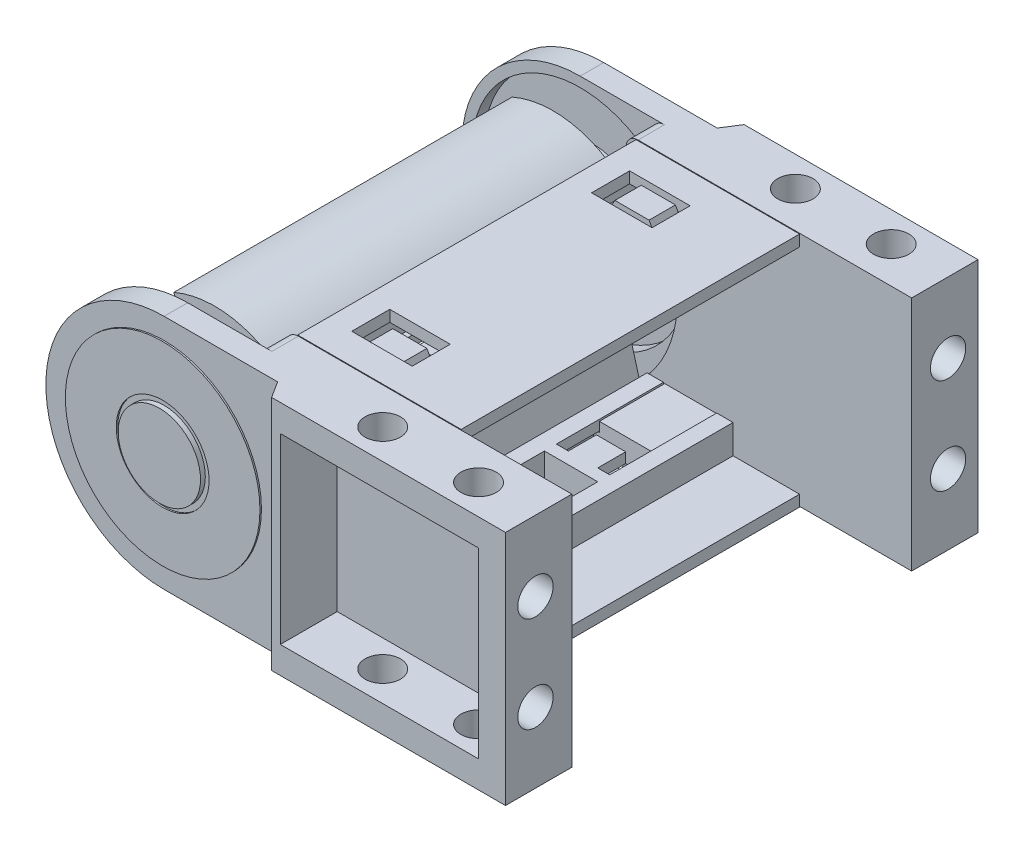
SolidWorks part; units mm, degrees
material "ABS"
ref_plane "Front Plane" through (0, 0, 0) normal (0, 0, 1) x (1, 0, 0)
ref_plane "Top Plane" through (0, 0, 0) normal (0, 1, 0) x (1, 0, 0)
ref_plane "Right Plane" through (0, 0, 0) normal (1, 0, 0) x (0, 0, -1)
sketch "Sketch1" plane through (0, 0, 0) normal (0, 0, 1) x (1, 0, 0)
  line L0 (0, 19.75) -> (59.75, 19.75)
  line L1 (59.75, 19.75) -> (59.75, -19.75)
  line L2 (59.75, -19.75) -> (0, -19.75)
  arc A0 (0, 19.75) -> (0, -19.75) centre (0, 0) ccw
  point P1 (-19.75, 0)
  dimension "D1" = 39.5
  dimension "D2" = 79.5
extrude "Boss-Extrude1" add sketch "Sketch1" against normal blind 11.08 from offset 39.45
sketch "Sketch2" plane through (0, 0, 39.45) normal (0, 0, 1) x (1, 0, 0)
  line L0 (59.75, -19.75) -> (59.75, 19.75) construction
  line L1 (22.15, 15.25) -> (55.25, 15.25)
  line L2 (22.15, 15.25) -> (22.15, -15.25)
  line L3 (22.15, -15.25) -> (55.25, -15.25)
  line L4 (55.25, 15.25) -> (55.25, -15.25)
  line L5 (38.7, -15.25) -> (38.7, 15.25) construction
  line L6 (22.15, 0) -> (55.25, 0) construction
  line L7 (59.75, 19.75) -> (0, 19.75) construction
  point P0 (38.7, 0)
  dimension "D1" = 4.5
  dimension "D2" = 4.5
  dimension "D3" = 33.1
extrude "Cut-Extrude1" cut sketch "Sketch2" against normal blind 9.5
sketch "Sketch3" plane through (0, 0, 39.45) normal (0, 0, 1) x (1, 0, 0)
  line L0 (0, -19.75) -> (59.75, -19.75) construction
  line L1 (59.75, 19.75) -> (0, 19.75) construction
  line L2 (0, -19.75) -> (18.95, -19.75)
  line L3 (18.95, 19.75) -> (0, 19.75)
  line L4 (18.95, 19.75) -> (18.95, -19.75)
  line L5 (59.75, -19.75) -> (59.75, 19.75) construction
  arc A0 (0, 19.75) -> (0, -19.75) centre (0, 0) ccw construction
  arc A1 (0, 19.75) -> (0, -19.75) centre (0, 0) ccw
  point P7 (-19.75, 0)
  dimension "D1" = 40.8
extrude "Cut-Extrude2" cut sketch "Sketch3" against normal blind 2.75
chamfer "Chamfer1" distance 1.75 distance2 2.75 1 edges at (18.95, 0, 39.45) first distance on face at (39.35, 0, 39.45)
sketch "Sketch5" plane through (0, 0, 36.7) normal (0, 0, 1) x (1, 0, 0)
  circle A0 centre (0, 0) radius 7.75
  circle A1 centre (0, 0) radius 16.25
  circle A2 centre (0, 0) radius 5.15
  dimension "D1" = 10.3
  dimension "D2" = 15.5
  dimension "D3" = 32.5
extrude "Boss-Extrude2" add sketch "Sketch5" along normal blind 0.25 contours A1 A0 region at (-15.7904, 0, 36.7)
extrude "Cut-Extrude3" cut sketch "Sketch5<3>" against normal through all contours A2 region at (0, 0, 36.7)
sketch "Sketch5<3>" plane through (0, 0, 36.7) normal (0, 0, 1) x (1, 0, 0) same geometry as "Sketch5"
sketch "Sketch6" plane through (0, 19.75, 0) normal (0, 1, 0) x (1, 0, 0)
  line L0 (59.75, -34.45) -> (20.7, -34.45) construction
  line L1 (59.75, -28.37) -> (59.75, -39.45) construction
  line L3 (59.75, -39.45) -> (20.7, -39.45) construction
  circle A0 centre (50.25, -34.45) radius 2.95
  circle A1 centre (34.25, -34.45) radius 2.95
  point P9 (0, 0)
  point P12 (0, 0)
  dimension "D1" = 5.9
  dimension "D2" = 16
  dimension "D3" = 9.5
  dimension "D4" = 5
extrude "Cut-Extrude4" cut sketch "Sketch6" against normal through all
sketch "Sketch7" plane through (59.75, 0, 0) normal (1, 0, 0) x (0, 0, -1)
  line L0 (-34.45, 19.75) -> (-34.45, -19.75) construction
  line L1 (-28.37, 19.75) -> (-39.45, 19.75) construction
  line L2 (-28.37, -19.75) -> (-39.45, -19.75) construction
  line L3 (-34.45, 0) -> (-28.37, 0) construction
  line L4 (-28.37, -19.75) -> (-28.37, 19.75) construction
  line L5 (-39.45, -19.75) -> (-39.45, 19.75) construction
  circle A0 centre (-34.45, 8) radius 2.95
  circle A1 centre (-34.45, -8) radius 2.95
  dimension "D1" = 16
  dimension "D2" = 5.9
  dimension "D3" = 5
extrude "Cut-Extrude5" cut sketch "Sketch7" against normal up to next
sketch "Sketch8" plane through (0, 0, 28.37) normal (0, 0, -1) x (-1, 0, 0)
  line L0 (19.75, 0) -> (-20.65, 0) construction
  circle A0 centre (0, 0) radius 20.65
  arc A1 (0, -19.75) -> (0, 19.75) centre (0, 0) ccw construction
  point P3 (-20.65, 0)
  point P4 (19.75, 0)
  dimension "D1" = 40.4
extrude "Cut-Extrude6" cut sketch "Sketch8" against normal blind 4.4
sketch "Sketch9" plane through (0, 0, 32.77) normal (0, 0, -1) x (-1, 0, 0)
  circle A0 centre (0, 0) radius 18.1
  dimension "D1" = 36.2
extrude "Cut-Extrude7" cut sketch "Sketch9" against normal blind 6.5 from surface starting at face at (36.545, 0, 28.37)
sketch "Sketch10" plane through (0, 0, 34.87) normal (0, 0, -1) x (-1, 0, 0)
  line L0 (0, 0) -> (16.75, 0) construction
  line L1 (8.5625, 2.5) -> (16.75, 3.2)
  line L2 (16.75, 3.2) -> (16.75, -3.2)
  line L3 (16.75, -3.2) -> (8.5625, -2.5)
  line L4 (8.8724, 0.9207) -> (15.15, 1.4574)
  line L5 (15.15, 1.4574) -> (15.15, -1.4574)
  line L6 (15.15, -1.4574) -> (8.8724, -0.9207)
  line L7 (8.6988, 0.9058) -> (15.15, 1.4574) construction
  line L8 (15.15, -1.4574) -> (8.6988, -0.9058) construction
  line L9 (0, 0) -> (0, -8.92) construction
  line L10 (-8.8724, 0.9207) -> (-15.15, 1.4574)
  line L11 (-15.15, 1.4574) -> (-15.15, -1.4574)
  line L12 (-15.15, -1.4574) -> (-8.8724, -0.9207)
  line L13 (-16.75, -3.2) -> (-8.5625, -2.5)
  line L14 (-16.75, 3.2) -> (-16.75, -3.2)
  line L15 (-8.5625, 2.5) -> (-16.75, 3.2)
  circle A0 centre (0, 0) radius 7
  arc A1 (-8.8724, 0.9207) -> (-8.8724, -0.9207) centre (0, 0) ccw
  arc A2 (-8.5625, -2.5) -> (8.5625, -2.5) centre (0, 0) ccw
  arc A3 (8.5625, 2.5) -> (-8.5625, 2.5) centre (0, 0) ccw
  arc A4 (8.8724, -0.9207) -> (8.8724, 0.9207) centre (0, 0) ccw
  point P7 (16.75, 0)
  dimension "D1" = 14
  dimension "D2" = 17.84
  dimension "D3" = 5
  dimension "D4" = 6.4
  dimension "D5" = 16.75
  dimension "D6" = 1.6
extrude "Boss-Extrude3" add sketch "Sketch10" along normal blind 3.9
fillet "Fillet1" radius 0.5 4 edges at (-16.75, -3.2, 32.92) (-16.75, 3.2, 32.92) (16.75, -3.2, 32.92) (16.75, 3.2, 32.92)
sketch "Sketch11" plane through (0, 0, 30.97) normal (0, 0, -1) x (-1, 0, 0)
  circle A0 centre (0, 0) radius 7 construction
  circle A1 centre (0, 0) radius 7
extrude "Cut-Extrude8" cut sketch "Sketch11" against normal blind 4.6
fillet "Fillet2" radius 2 2 edges at (6.0299, 19.75, 30.57) (6.0299, -19.75, 30.57)
sketch "Sketch12" plane through (0, 0, 28.37) normal (0, 0, -1) x (-1, 0, 0)
  line L0 (-27.425, 17.15) -> (-18.325, 17.15)
  line L1 (-22.875, 17.15) -> (-22.875, 13.25) construction
  line L2 (-27.425, 17.15) -> (-28.25, 15.65)
  line L3 (-28.25, 14.85) -> (-27.225, 14.85)
  line L4 (-27.225, 14.85) -> (-27.225, 13.25)
  line L5 (-18.525, 14.85) -> (-18.525, 13.25)
  line L6 (-17.5, 14.85) -> (-18.525, 14.85)
  line L7 (-18.325, 17.15) -> (-17.5, 15.65)
  line L8 (-18.525, 13.25) -> (-27.225, 13.25)
  line L9 (-28.25, 15.65) -> (-28.25, 14.85)
  line L10 (0, 0) -> (-59.75, 0) construction
  line L11 (-59.75, -19.75) -> (-59.75, 19.75) construction
  line L20 (-17.5, 15.65) -> (-17.5, 14.85)
  line L21 (-22.875, -17.15) -> (-22.875, -13.25) construction
  line L22 (-17.5, -15.65) -> (-17.5, -14.85)
  line L23 (-28.25, -15.65) -> (-28.25, -14.85)
  line L24 (-18.525, -13.25) -> (-27.225, -13.25)
  line L25 (-18.325, -17.15) -> (-17.5, -15.65)
  line L26 (-17.5, -14.85) -> (-18.525, -14.85)
  line L27 (-18.525, -14.85) -> (-18.525, -13.25)
  line L28 (-27.225, -14.85) -> (-27.225, -13.25)
  line L29 (-28.25, -14.85) -> (-27.225, -14.85)
  line L30 (-27.425, -17.15) -> (-28.25, -15.65)
  line L31 (-27.425, -17.15) -> (-18.325, -17.15)
  point P3 (-22.875, 17.15)
  point P5 (-27.225, 14.05)
  dimension "D1" = 10.75
  dimension "D2" = 31.5
  dimension "D3" = 26.5
  dimension "D4" = 34.3
  dimension "D5" = 8.7
  dimension "D6" = 2.3
  dimension "D7" = 0.8
  dimension "D8" = 9.1
extrude "Boss-Extrude4" add sketch "Sketch12" along normal offset from surface (10.92 mm away) 22 up to face at (40.225, 0, 39.45)
sketch "Sketch13" plane through (0, 0, 17.45) normal (0, 0, -1) x (-1, 0, 0)
  line L0 (-26.7, 17.15) -> (-25.725, 18.9)
  line L1 (-18.325, 17.15) -> (-27.425, 17.15) construction
  line L2 (-25.725, 18.9) -> (-20.025, 18.9)
  line L3 (-20.025, 18.9) -> (-19.05, 17.15)
  line L4 (-26.7, 17.15) -> (-19.05, 17.15)
  line L5 (-22.875, 18.9) -> (-22.875, 17.15) construction
  line L6 (0, 0) -> (-59.75, 0) construction
  line L7 (-59.75, -19.75) -> (-59.75, 19.75) construction
  line L8 (-20.025, -18.9) -> (-19.05, -17.15)
  line L9 (-26.7, -17.15) -> (-19.05, -17.15)
  line L10 (-26.7, -17.15) -> (-25.725, -18.9)
  line L11 (-25.725, -18.9) -> (-20.025, -18.9)
  point P8 (-22.875, 17.15)
  dimension "D1" = 7.65
  dimension "D2" = 5.7
  dimension "D3" = 1.75
extrude "Boss-Extrude5" add sketch "Sketch13" against normal blind 4.4 from offset 1.1 offset against normal yes
sketch "Sketch14" plane through (0, 0, 0) normal (0, 0, 1) x (1, 0, 0)
  line L0 (41.15, 19.75) -> (13.85, 19.75)
  line L1 (59.75, 19.75) -> (14.0698, 19.75) construction
  line L2 (13.85, 19.75) -> (11.7872, 12.25)
  line L3 (59.75, -19.75) -> (59.75, 19.75) construction
  line L4 (41.15, 17.87) -> (30.05, 17.87)
  line L5 (15.2827, 17.87) -> (12.6469, 8.2867)
  line L6 (-6.85, 15.5588) -> (-6.0925, 13.8382)
  line L7 (41.15, 19.75) -> (41.15, 17.87)
  line L8 (30.05, 13.05) -> (30.05, 17.87)
  line L9 (27.325, 13.05) -> (30.05, 13.05)
  line L10 (27.325, 13.05) -> (27.325, 14.75)
  line L11 (27.325, 14.75) -> (28.35, 14.75)
  line L12 (28.35, 14.75) -> (28.35, 17.87)
  line L13 (28.35, 17.87) -> (17.4, 17.87)
  line L14 (41.15, 17.87) -> (15.2827, 17.87) construction
  line L15 (18.425, 13.05) -> (15.7, 13.05)
  line L16 (15.7, 13.05) -> (15.7, 17.87)
  line L17 (22.875, 13.25) -> (22.875, 19.75) construction
  line L18 (18.425, 13.25) -> (18.425, 14.75)
  line L19 (17.4, 14.75) -> (17.4, 15.65)
  line L20 (18.425, 14.75) -> (17.4, 14.75)
  line L21 (18.425, 13.05) -> (18.425, 14.75)
  line L22 (17.4, 14.75) -> (17.4, 17.87)
  line L23 (18.425, 14.75) -> (17.4, 14.75)
  line L24 (18.525, 13.25) -> (27.225, 13.25) construction
  line L25 (15.7, 17.87) -> (15.2827, 17.87)
  arc A0 (11.7872, 12.25) -> (-6.85, 15.5588) centre (0, 0) ccw
  arc A1 (12.6469, 8.2867) -> (-6.0925, 13.8382) centre (0, 0) ccw
  dimension "D1" = 17
  dimension "D2" = 48
  dimension "D3" = 27.3
  dimension "D4" = 7.5
  dimension "D5" = 18.6
  dimension "D7" = 0.1
  dimension "D6" = 1.88
  dimension "D8" = 1.7
extrude "Boss-Extrude6" add sketch "Sketch14" along normal mid plane 56.5 separate body
sketch "Sketch15" plane through (0, 19.75, 0) normal (0, 1, 0) x (1, 0, 0)
  line L1 (27.925, -16.85) -> (17.825, -16.85)
  line L2 (27.925, -16.85) -> (27.925, -23.2)
  line L5 (27.925, -23.2) -> (17.825, -23.2)
  line L6 (17.825, -16.85) -> (17.825, -23.2)
  line L7 (22.875, -23.2) -> (22.875, -16.85) construction
  line L8 (27.925, -20.025) -> (17.825, -20.025) construction
  line L9 (0, 0) -> (44.1536, 0) construction
  line L10 (17.825, 16.85) -> (17.825, 23.2)
  line L11 (27.925, 23.2) -> (17.825, 23.2)
  line L12 (27.925, 16.85) -> (27.925, 23.2)
  line L13 (27.925, 16.85) -> (17.825, 16.85)
  line L14 (19.05, -18.55) -> (26.7, -22.95) construction
  point P14 (22.875, -20.75)
  point P172 (22.875, -20.025)
  dimension "D1" = 10.1
  dimension "D2" = 33.7
  dimension "D3" = 46.4
extrude "Cut-Extrude9" cut sketch "Sketch15" against normal up to surface (5 mm away) up to face at (27.8375, 14.75, 0)
sketch "Sketch16" plane through (0, 13.05, 0) normal (0, -1, 0) x (1, 0, 0)
  line L0 (30.05, 28.25) -> (30.05, -28.25) construction
  line L1 (30.05, 10.375) -> (15.7, 10.375)
  line L2 (30.05, 10.375) -> (30.05, -10.375)
  line L3 (30.05, -10.375) -> (15.7, -10.375)
  line L4 (15.7, 10.375) -> (15.7, -10.375)
  line L5 (22.875, -10.375) -> (22.875, 10.375) construction
  line L6 (30.05, 0) -> (15.7, 0) construction
  line L7 (15.7, 28.25) -> (15.7, -28.25) construction
  line L8 (18.425, 28.25) -> (18.425, -28.25) construction
  line L9 (27.325, -8.375) -> (18.425, -8.375)
  line L10 (27.325, -8.375) -> (27.325, 8.375)
  line L11 (27.325, 8.375) -> (18.425, 8.375)
  line L12 (18.425, -8.375) -> (18.425, 8.375)
  line L13 (22.875, 8.375) -> (22.875, -8.375) construction
  line L14 (27.325, 0) -> (18.425, 0) construction
  point P10 (22.875, 0)
  point P212 (22.875, 0)
  dimension "D1" = 20.75
  dimension "D2" = 2
extrude "Boss-Extrude7" add sketch "Sketch16" against normal up to surface (4.82 mm away) up to face at (35.6, 17.87, 0)
sketch "Sketch17" plane through (0, 13.05, 0) normal (0, -1, 0) x (1, 0, 0)
  line L0 (22.875, 10.375) -> (22.875, -10.375) construction
  line L1 (28.35, 10.375) -> (17.4, 10.375) construction
  line L2 (18.425, -10.375) -> (27.325, -10.375) construction
  line L3 (25.325, 10.375) -> (25.325, 15.05)
  line L4 (20.425, 10.375) -> (20.425, 15.05)
  line L5 (20.425, 15.05) -> (25.325, 15.05)
  line L6 (22.875, 0) -> (41.15, 0) construction
  line L7 (41.15, 28.25) -> (41.15, -28.25) construction
  line L8 (25.325, 10.375) -> (20.425, 10.375)
  line L9 (20.425, -10.375) -> (20.425, -15.05)
  line L10 (20.425, -15.05) -> (25.325, -15.05)
  line L11 (25.325, -10.375) -> (25.325, -15.05)
  line L12 (25.325, -10.375) -> (20.425, -10.375)
  dimension "D1" = 4.9
  dimension "D2" = 30.1
extrude "Boss-Extrude8" add sketch "Sketch17" against normal up to surface (1.7 mm away) up to face at (17.9125, 14.75, 19.3125)
sketch "Sketch18" plane through (0, 0, 36.7) normal (0, 0, 1) x (1, 0, 0)
  circle A0 centre (0, 0) radius 6.875
  dimension "D1" = 13.75
extrude "Boss-Extrude9" add sketch "Sketch18" along normal blind 0.8 separate body
sketch "Sketch19" plane through (0, 0, 36.7) normal (0, 0, -1) x (-1, 0, 0)
  circle A2 centre (0, 0) radius 5.1
  circle A3 centre (0, 0) radius 5.1
  dimension "D1" = 0.05
extrude "Boss-Extrude10" add sketch "Sketch19" along normal blind 8
mirror "Mirror1" about plane through (0, 0, 0) normal (0, 0, 1) of bodies 113 121
mirror "Mirror2" about plane through (0, 0, 0) normal (0, 1, 0) of bodies 119 115
